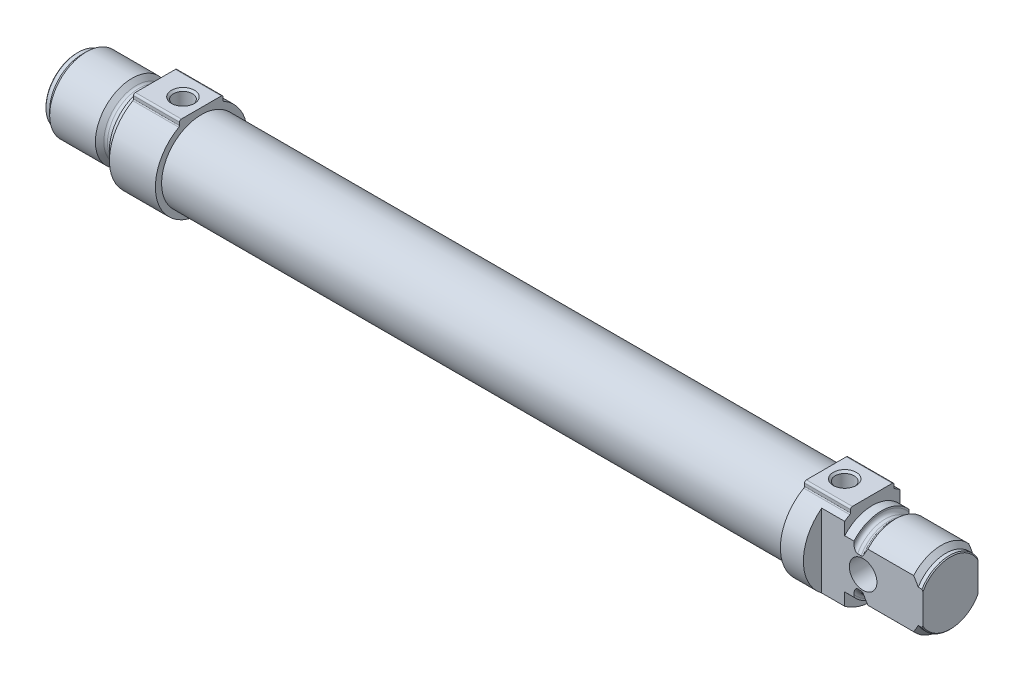
SolidWorks part; units mm, degrees
ref_plane "Ebene vorne" through (0, 0, 0) normal (0, 0, 1) x (1, 0, 0)
ref_plane "Ebene oben" through (0, 0, 0) normal (0, 1, 0) x (1, 0, 0)
ref_plane "Ebene rechts" through (0, 0, 0) normal (1, 0, 0) x (0, 0, -1)
sketch "Skizze1" plane through (0, 0, 0) normal (0, 0, 1) x (1, 0, 0)
  line L0 (0, 0) -> (0, 6.8)
  line L1 (0, 6.8) -> (0.2, 7)
  line L2 (0.2, 7) -> (1, 7)
  line L3 (1, 7) -> (2, 8)
  line L4 (2, 8) -> (11.95, 8)
  line L5 (11.95, 8) -> (12.8657, 7.0843)
  line L6 (13.4314, 6.85) -> (14.2, 6.85)
  line L7 (15, 7.65) -> (15, 8)
  line L8 (15, 8) -> (17, 8)
  line L9 (17, 8) -> (17, 0)
  line L10 (17, 0) -> (0, 0)
  line L11 (17, 0) -> (0, 0) construction
  arc A0 (12.8657, 7.0843) -> (13.4314, 6.85) centre (13.4314, 7.65) ccw
  arc A1 (14.2, 6.85) -> (15, 7.65) centre (14.2, 7.65) ccw
revolve "Rotation1" add sketch "Skizze1" angle 360 about L11 reverse direction yes
cosmetic thread "Gewindedarstellung1" parameters "D1"=10.87, "D2"=14.16
ref_plane "Ebene1" through (21.1, 0, 0) normal (1, 0, 0) x (0, 0, -1)
ref_plane "Ebene2" through (9, 0, 0) normal (1, 0, 0) x (0, 0, -1)
ref_plane "Ebene3" through (0, -11, 0) normal (0, 1, 0) x (1, 0, 0)
ref_plane "Ebene4" through (0, 11, 0) normal (0, 1, 0) x (1, 0, 0)
ref_plane "Ebene5" through (0, 0, 0) normal (0, 1, 0) x (1, 0, 0)
ref_plane "Ebene6" through (0, 0, 0) normal (0, 1, 0) x (1, 0, 0)
ref_plane "Ebene7" through (17, 0, 0) normal (1, 0, 0) x (0, 0, -1)
ref_plane "Ebene8" through (17, 0, 0) normal (1, 0, 0) x (0, 0, -1)
ref_plane "Ebene9" through (27, 0, 0) normal (1, 0, 0) x (0, 0, -1)
ref_plane "Ebene10" through (17, 0, 0) normal (1, 0, 0) x (0, 0, -1)
ref_plane "Ebene11" through (17, 0, 0) normal (1, 0, 0) x (0, 0, -1)
sketch "Skizze2" plane through (17, 0, 0) normal (1, 0, 0) x (0, 0, -1)
  line L0 (4.75, 8.9771) -> (4.75, 9.6)
  line L1 (4.35, 10) -> (-4.35, 10)
  line L2 (-4.75, 9.6) -> (-4.75, 8.9771)
  arc A0 (-4.9029, 8.7156) -> (4.9029, 8.7156) centre (0, 0) ccw
  arc A1 (4.9029, 8.7156) -> (4.75, 8.9771) centre (5.05, 8.9771) cw
  arc A2 (4.75, 9.6) -> (4.35, 10) centre (4.35, 9.6) ccw
  arc A3 (-4.35, 10) -> (-4.75, 9.6) centre (-4.35, 9.6) ccw
  arc A4 (-4.75, 8.9771) -> (-4.9029, 8.7156) centre (-5.05, 8.9771) cw
extrude "Aufsatz-Linear austragen1" add sketch "Skizze2" along normal blind 10
ref_plane "Ebene12" through (23, 0, 0) normal (1, 0, 0) x (0, 0, -1)
ref_plane "Ebene13" through (0, 0, 0) normal (0, 0, 1) x (1, 0, 0)
ref_plane "Ebene14" through (0, 0, -6.5) normal (0, 0, 1) x (1, 0, 0)
ref_plane "Ebene15" through (0, 0, 0) normal (0, 1, 0) x (1, 0, 0)
ref_plane "Ebene16" through (0, 5.5, 0) normal (0, 1, 0) x (1, 0, 0)
ref_plane "Ebene17" through (0, 0, -6.6) normal (0, 0, 1) x (1, 0, 0)
ref_plane "Ebene18" through (0, 0, 0) normal (0, 1, 0) x (1, 0, 0)
ref_plane "Ebene19" through (0, 5.5, 0) normal (0, 1, 0) x (1, 0, 0)
ref_plane "Ebene20" through (0, 6.4628, -1.1396) normal (0, 0.9848, -0.1736) x (1, 0, 0)
ref_plane "Ebene21" through (0, 4.9856, -0.8791) normal (0, 0.9848, -0.1736) x (1, 0, 0)
sketch "Skizze3" plane through (0, 0, 0) normal (0, 0, 1) x (1, 0, 0)
  line L0 (27, 0) -> (27, 8.65)
  line L1 (27, 8.65) -> (163, 8.65)
  line L2 (163, 8.65) -> (163, 0)
  line L3 (163, 0) -> (27, 0)
  line L4 (163, 0) -> (27, 0) construction
revolve "Rotation2" add sketch "Skizze3" angle 360 about L4 reverse direction yes
ref_plane "Ebene22" through (163, 0, 0) normal (1, 0, 0) x (0, 0, -1)
sketch "Skizze4" plane through (163, 0, 0) normal (1, 0, 0) x (0, 0, -1)
  line L0 (4.75, 8.9771) -> (4.75, 9.6)
  line L1 (4.35, 10) -> (-4.35, 10)
  line L2 (-4.75, 9.6) -> (-4.75, 8.9771)
  arc A0 (-4.9029, 8.7156) -> (4.9029, 8.7156) centre (0, 0) ccw
  arc A1 (4.9029, 8.7156) -> (4.75, 8.9771) centre (5.05, 8.9771) cw
  arc A2 (4.75, 9.6) -> (4.35, 10) centre (4.35, 9.6) ccw
  arc A3 (-4.35, 10) -> (-4.75, 9.6) centre (-4.35, 9.6) ccw
  arc A4 (-4.75, 8.9771) -> (-4.9029, 8.7156) centre (-5.05, 8.9771) cw
extrude "Aufsatz-Linear austragen2" add sketch "Skizze4" along normal blind 10
ref_plane "Ebene23" through (165.35, 0, 0) normal (1, 0, 0) x (0, 0, -1)
ref_plane "Ebene24" through (167, 0, 0) normal (1, 0, 0) x (0, 0, -1)
ref_plane "Ebene25" through (0, 0, 6.6) normal (0, 0, 1) x (1, 0, 0)
ref_plane "Ebene26" through (0, 0, 0) normal (0, 1, 0) x (1, 0, 0)
ref_plane "Ebene27" through (0, 5.5, 0) normal (0, 1, 0) x (1, 0, 0)
ref_plane "Ebene28" through (0, 6.4628, 1.1396) normal (0, 0.9848, 0.1736) x (1, 0, 0)
ref_plane "Ebene29" through (0, 4.9856, 0.8791) normal (0, 0.9848, 0.1736) x (1, 0, 0)
ref_plane "Ebene30" through (211, 0, 0) normal (1, 0, 0) x (0, 0, -1)
sketch "Skizze5" plane through (0, 0, 0) normal (0, 0, 1) x (1, 0, 0)
  line L0 (173, 0) -> (173, 8)
  line L1 (173, 8) -> (175, 8)
  line L2 (175, 8) -> (175, 7.65)
  line L3 (175.8, 6.85) -> (176.5686, 6.85)
  line L4 (177.1343, 7.0843) -> (178.05, 8)
  line L5 (178.05, 8) -> (188, 8)
  line L6 (188, 8) -> (189, 7)
  line L7 (189, 7) -> (189.8, 7)
  line L8 (189.8, 7) -> (190, 6.8)
  line L9 (190, 6.8) -> (190, 0)
  line L10 (190, 0) -> (173, 0)
  line L11 (190, 0) -> (173, 0) construction
  arc A0 (175, 7.65) -> (175.8, 6.85) centre (175.8, 7.65) ccw
  arc A1 (176.5686, 6.85) -> (177.1343, 7.0843) centre (176.5686, 7.65) ccw
revolve "Rotation3" add sketch "Skizze5" angle 360 about L11 reverse direction yes
cosmetic thread "Gewindedarstellung2" parameters "D1"=9.87, "D2"=14.16
ref_plane "Ebene31" through (201, 0, 0) normal (1, 0, 0) x (0, 0, -1)
ref_plane "Ebene32" through (211, 0, 0) normal (1, 0, 0) x (0, 0, -1)
ref_plane "Ebene33" through (211, 0, 0) normal (1, 0, 0) x (0, 0, -1)
sketch "Skizze6" plane through (0, 0, 0) normal (0, 1, 0) x (1, 0, 0)
  line L0 (168, 18) -> (168, 6)
  line L1 (168, 6) -> (190, 6)
  line L2 (190, 6) -> (190, -6)
  line L3 (190, -6) -> (168, -6)
  line L4 (168, -6) -> (168, -18)
  line L5 (168, -18) -> (202, -18)
  line L6 (202, -18) -> (202, 18)
  line L7 (202, 18) -> (168, 18)
extrude "Schnitt-Linear austragen1" cut sketch "Skizze6" along normal blind 10 and the other way blind 10
ref_plane "Ebene34" through (177, 0, 0) normal (1, 0, 0) x (0, 0, -1)
hole_wizard "Bohrung1" positions "Skizze8" profile "Skizze7" legacy
sketch "Skizze8" plane through (0, 0, -6) normal (0, 0, -1) x (-1, 0, 0)
  point P0 (-177, 0)
sketch "Skizze7" plane through (177, 0, -6) normal (1, 0, 0) x (0, 1, 0)
  line L0 (0, 0) -> (0, 12)
  line L1 (0, 12) -> (3, 12)
  line L2 (3, 12) -> (3, 0)
  line L3 (3, 0) -> (0, 0)
  line L4 (0, 110) -> (0, -10) construction
  dimension "Durchmesser" = 6
  dimension "Tiefe" = 12
hole_wizard "Bohrung2" positions "Skizze10" profile "Skizze9" legacy
sketch "Skizze10" plane through (0, 10, 0) normal (0, 1, 0) x (1, 0, 0)
  point P0 (23, 0)
sketch "Skizze9" plane through (23, 10, 0) normal (1, 0, 0) x (0, 0, 1)
  line L0 (0, 0) -> (0, 10)
  line L1 (0, 10) -> (2.067, 10)
  line L2 (2.067, 10) -> (2.067, 0.433)
  line L3 (2.067, 0.433) -> (2.5, 0)
  line L4 (2.5, 0) -> (0, 0)
  line L5 (0, -6.4453) -> (0, 115.525) construction
  line L6 (-2.067, 0.433) -> (-2.5, 0) construction
  dimension "Durchmesser" = 4.134
  dimension "Tiefe" = 10
  dimension "Senkwinkel1" = 90
  dimension "Senkdurchmesser3" = 5
cosmetic thread "Gewindedarstellung3" parameters "D1"=7, "D2"=5
hole_wizard "Bohrung3" positions "Skizze12" profile "Skizze11" legacy
sketch "Skizze12" plane through (0, 10, 0) normal (0, 1, 0) x (1, 0, 0)
  point P0 (167, 0)
sketch "Skizze11" plane through (167, 10, 0) normal (1, 0, 0) x (0, 0, 1)
  line L0 (0, 0) -> (0, 12.1934)
  line L1 (0, 12.1934) -> (2.067, 11)
  line L2 (2.067, 11) -> (2.067, 0.433)
  line L3 (2.067, 0.433) -> (2.5, 0)
  line L4 (2.5, 0) -> (0, 0)
  line L5 (0, -14.3089) -> (0, 102.4216) construction
  line L6 (0, 12.1934) -> (-2.067, 11) construction
  line L7 (-2.067, 0.433) -> (-2.5, 0) construction
  dimension "Durchmesser" = 4.134
  dimension "Tiefe" = 11
  dimension "Senkdurchmesser1" = 5
  dimension "Senkwinkel1" = 90
  dimension "Spitzenwinkel" = 120
cosmetic thread "Gewindedarstellung4" parameters "D1"=6, "D2"=5
sketch "Skizze13" plane through (0, 0, 0) normal (0, 0, 1) x (1, 0, 0)
  line L0 (-5, 0) -> (-5, 3)
  line L1 (-5, 3) -> (41.2, 3)
  line L2 (41.2, 3) -> (41.2, 8)
  line L3 (41.2, 8) -> (145.2, 8)
  line L4 (145.2, 8) -> (145.2, 0)
  line L5 (145.2, 0) -> (-5, 0)
  line L6 (145.2, 0) -> (-5, 0) construction
revolve "Schnitt-Rotation1" cut sketch "Skizze13" angle 360 about L6 reverse direction yes
ref_plane "Ebene35" through (-5, 0, 0) normal (1, 0, 0) x (0, 0, -1)
ref_plane "Ebene36" through (0, 10, 0) normal (0, 1, 0) x (1, 0, 0)
ref_plane "Ebene37" through (7, 0, 0) normal (1, 0, 0) x (0, 0, -1)
ref_plane "Ebene38" through (0, 0, 0) normal (1, 0, 0) x (0, 0, -1)
ref_plane "Ebene39" through (17, 0, 0) normal (1, 0, 0) x (0, 0, -1)
ref_plane "Ebene40" through (173, 0, 0) normal (1, 0, 0) x (0, 0, -1)
ref_plane "Ebene41" through (17, 0, 0) normal (1, 0, 0) x (0, 0, -1)
ref_plane "Ebene42" through (0, 10, 0) normal (0, 1, 0) x (1, 0, 0)
ref_plane "Ebene43" through (36.5, 0, 0) normal (1, 0, 0) x (0, 0, -1)
ref_plane "Ebene44" through (153.5, 0, 0) normal (1, 0, 0) x (0, 0, -1)
ref_plane "Ebene45" through (0, 0, 0) normal (0, 0, 1) x (1, 0, 0)
ref_plane "Ebene46" through (17, 0, 0) normal (1, 0, 0) x (0, 0, -1)
ref_plane "Ebene47" through (0, 10, 0) normal (0, 1, 0) x (1, 0, 0)
ref_plane "FDT_FRONT XY" through (17, 0, 0) normal (1, 0, 0) x (0, 0, -1)
ref_plane "FDT_FRONT XZ" through (0, 0, 0) normal (0, -1, 0) x (-1, 0, 0)
ref_plane "FDT_FRONT YZ" through (0, 0, 0) normal (0, 0, -1) x (-1, 0, 0)
ref_axis "FDT_FRONT X" through (17, 0, 80.9) along (0, 0, -1)
ref_axis "FDT_FRONT Y" through (17, -50, 0) along (0, 1, 0)
ref_axis "FDT_FRONT Z" through (80.9, 0, 0) along (-1, 0, 0)
sketch3d "FDT_FRONT"
  point P0 (17, 0, 0)
ref_plane "FDT_QSFRONT XY" through (0, 10, 0) normal (0, 1, 0) x (1, 0, 0)
ref_plane "FDT_QSFRONT XZ" through (23, 0, 0) normal (-1, 0, 0) x (0, 0, 1)
ref_plane "FDT_QSFRONT YZ" through (0, 0, 0) normal (0, 0, 1) x (1, 0, 0)
ref_axis "FDT_QSFRONT X" through (23, 10, -50) along (0, 0, 1)
ref_axis "FDT_QSFRONT Y" through (-80.9, 10, 0) along (1, 0, 0)
ref_axis "FDT_QSFRONT Z" through (23, 50, 0) along (0, -1, 0)
sketch3d "FDT_QSFRONT"
  point P0 (23, 10, 0)
ref_plane "FDT_QSREAR XY" through (0, 10, 0) normal (0, 1, 0) x (1, 0, 0)
ref_plane "FDT_QSREAR XZ" through (167, 0, 0) normal (-1, 0, 0) x (0, 0, 1)
ref_plane "FDT_QSREAR YZ" through (0, 0, 0) normal (0, 0, 1) x (1, 0, 0)
ref_axis "FDT_QSREAR X" through (167, 10, -50) along (0, 0, 1)
ref_axis "FDT_QSREAR Y" through (-80.9, 10, 0) along (1, 0, 0)
ref_axis "FDT_QSREAR Z" through (167, 50, 0) along (0, -1, 0)
sketch3d "FDT_QSREAR"
  point P0 (167, 10, 0)
ref_plane "FDT_REAR XY" through (173, 0, 0) normal (-1, 0, 0) x (0, 0, 1)
ref_plane "FDT_REAR XZ" through (0, 0, 0) normal (0, 1, 0) x (1, 0, 0)
ref_plane "FDT_REAR YZ" through (0, 0, 0) normal (0, 0, -1) x (-1, 0, 0)
ref_axis "FDT_REAR X" through (173, 0, 80.9) along (0, 0, -1)
ref_axis "FDT_REAR Y" through (173, 50, 0) along (0, -1, 0)
ref_axis "FDT_REAR Z" through (-80.9, 0, 0) along (1, 0, 0)
sketch3d "FDT_REAR"
  point P0 (173, 0, 0)
ref_plane "FDT_SMBR1 XY" through (36.5, 0, 0) normal (-1, 0, 0) x (0, 0, 1)
ref_plane "FDT_SMBR1 XZ" through (0, 0, 0) normal (0, -1, 0) x (-1, 0, 0)
ref_plane "FDT_SMBR1 YZ" through (0, 0, 0) normal (0, 0, 1) x (1, 0, 0)
ref_axis "FDT_SMBR1 X" through (36.5, 0, -80.9) along (0, 0, 1)
ref_axis "FDT_SMBR1 Y" through (36.5, -50, 0) along (0, 1, 0)
ref_axis "FDT_SMBR1 Z" through (-80.9, 0, 0) along (1, 0, 0)
sketch3d "FDT_SMBR1"
  point P0 (36.5, 0, 0)
ref_plane "FDT_SMBR2 XY" through (153.5, 0, 0) normal (-1, 0, 0) x (0, 0, 1)
ref_plane "FDT_SMBR2 XZ" through (0, 0, 0) normal (0, -1, 0) x (-1, 0, 0)
ref_plane "FDT_SMBR2 YZ" through (0, 0, 0) normal (0, 0, 1) x (1, 0, 0)
ref_axis "FDT_SMBR2 X" through (153.5, 0, -80.9) along (0, 0, 1)
ref_axis "FDT_SMBR2 Y" through (153.5, -50, 0) along (0, 1, 0)
ref_axis "FDT_SMBR2 Z" through (-80.9, 0, 0) along (1, 0, 0)
sketch3d "FDT_SMBR2"
  point P0 (153.5, 0, 0)
ref_plane "FDT_SWIVELAXIS XY" through (0, 0, 0) normal (0, 0, 1) x (1, 0, 0)
ref_plane "FDT_SWIVELAXIS XZ" through (0, 0, 0) normal (0, -1, 0) x (-1, 0, 0)
ref_plane "FDT_SWIVELAXIS YZ" through (177, 0, 0) normal (1, 0, 0) x (0, 0, -1)
ref_axis "FDT_SWIVELAXIS X" through (-80.9, 0, 0) along (1, 0, 0)
ref_axis "FDT_SWIVELAXIS Y" through (177, -50, 0) along (0, 1, 0)
ref_axis "FDT_SWIVELAXIS Z" through (177, 0, 80.9) along (0, 0, -1)
sketch3d "FDT_SWIVELAXIS"
  point P0 (177, 0, 0)
ref_plane "NUT XY" through (7, 0, 0) normal (1, 0, 0) x (0, 0, -1)
ref_plane "NUT XZ" through (0, 0, 0) normal (0, -1, 0) x (-1, 0, 0)
ref_plane "NUT YZ" through (0, 0, 0) normal (0, 0, -1) x (-1, 0, 0)
ref_axis "NUT X" through (7, 0, 80.9) along (0, 0, -1)
ref_axis "NUT Y" through (7, -50, 0) along (0, 1, 0)
ref_axis "NUT Z" through (80.9, 0, 0) along (-1, 0, 0)
sketch3d "NUT"
  point P0 (7, 0, 0)
ref_plane "ZR XY" through (0, 0, 0) normal (1, 0, 0) x (0, 0, -1)
ref_plane "ZR XZ" through (0, 0, 0) normal (0, -1, 0) x (-1, 0, 0)
ref_plane "ZR YZ" through (0, 0, 0) normal (0, 0, -1) x (-1, 0, 0)
ref_axis "ZR X" through (0, 0, 80.9) along (0, 0, -1)
ref_axis "ZR Y" through (0, -50, 0) along (0, 1, 0)
ref_axis "ZR Z" through (80.9, 0, 0) along (-1, 0, 0)
sketch3d "ZR"
  point P0 (0, 0, 0)
ref_plane "ZYL XY" through (17, 0, 0) normal (1, 0, 0) x (0, 0, -1)
ref_plane "ZYL XZ" through (0, 0, 0) normal (0, -1, 0) x (-1, 0, 0)
ref_plane "ZYL YZ" through (0, 0, 0) normal (0, 0, -1) x (-1, 0, 0)
ref_axis "ZYL X" through (17, 0, 80.9) along (0, 0, -1)
ref_axis "ZYL Y" through (17, -50, 0) along (0, 1, 0)
ref_axis "ZYL Z" through (80.9, 0, 0) along (-1, 0, 0)
sketch3d "ZYL"
  point P0 (17, 0, 0)
